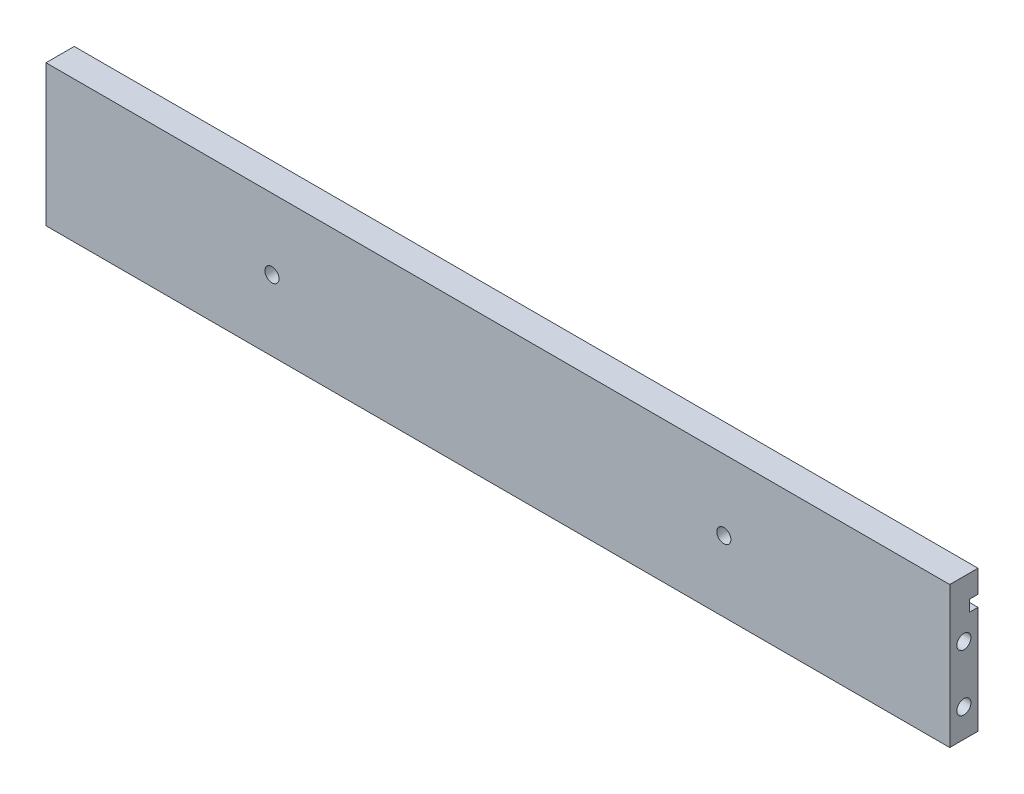
SolidWorks part; units mm, degrees
ref_plane "Ön Düzlem" through (0, 0, 0) normal (0, 0, 1) x (1, 0, 0)
ref_plane "Üst Düzlem" through (0, 0, 0) normal (0, 1, 0) x (1, 0, 0)
ref_plane "Sağ Düzlem" through (0, 0, 0) normal (1, 0, 0) x (0, 0, -1)
sketch "Sketch1" plane through (0, 0, 0) normal (0, 0, 1) x (1, 0, 0)
  line L1 (0, 0) -> (160, 0)
  line L2 (0, 0) -> (0, 25)
  line L3 (0, 25) -> (160, 25)
  line L4 (160, 0) -> (160, 25)
extrude "Boss-Extrude1" add sketch "Sketch1" along normal blind 5
sketch "Sketch2" plane through (0, 0, 0) normal (0, -1, 0) x (1, 0, 0)
  line L0 (0, 5) -> (0, 0) construction
  line L1 (160, 5) -> (160, 0) construction
  line L2 (0, 5) -> (160, 5) construction
  circle A0 centre (40, 2.5) radius 1.25
  circle A1 centre (120, 2.5) radius 1.24
  dimension "D1" = 40
  dimension "D2" = 40
  dimension "D3" = 2.5
  dimension "D4" = 2.5
extrude "Cut-Extrude1" cut sketch "Sketch2" against normal blind 10
cosmetic thread "Cosmetic Thread1" parameters "D2"=3
cosmetic thread "Cosmetic Thread2" parameters "D2"=3
sketch "Sketch5" plane through (0, 0, 0) normal (-1, 0, 0) x (0, 0, 1)
  line L0 (0, 25) -> (0, 0) construction
  line L1 (1.5, 21) -> (0, 21)
  line L2 (1.5, 21) -> (1.5, 19)
  line L3 (1.5, 19) -> (0, 19)
  line L4 (0, 21) -> (0, 19)
  line L5 (5, 25) -> (0, 25) construction
  dimension "D1" = 4
  dimension "D2" = 2
  dimension "D3" = 1.5
extrude "Cut-Extrude4" cut sketch "Sketch5" against normal through all
sketch "Sketch6" plane through (0, 0, 5) normal (0, 0, 1) x (1, 0, 0)
  line L0 (0, 25) -> (0, 0) construction
  line L1 (160, 25) -> (0, 25) construction
  line L2 (160, 0) -> (160, 25) construction
  circle A0 centre (40, 12.5) radius 1.25
  circle A1 centre (120, 12.5) radius 1.25
  dimension "D1" = 40
  dimension "D2" = 12.5
  dimension "D3" = 40
  dimension "D4" = 12.5
extrude "Cut-Extrude5" cut sketch "Sketch6" against normal blind 10
cosmetic thread "Cosmetic Thread3" parameters "D2"=3
cosmetic thread "Cosmetic Thread4" parameters "D2"=3
sketch "Sketch7" plane through (0, 0, 0) normal (-1, 0, 0) x (0, 0, 1)
  line L0 (5, 0) -> (0, 0) construction
  line L1 (5, 25) -> (5, 0) construction
  line L3 (0, 19) -> (0, 0) construction
  circle A0 centre (2.5, 5) radius 1.25
  circle A1 centre (2.5, 15) radius 1.25
  dimension "D1" = 5
  dimension "D2" = 2.5
  dimension "D3" = 2.5
  dimension "D4" = 10
extrude "Cut-Extrude6" cut sketch "Sketch7" against normal blind 10
cosmetic thread "Cosmetic Thread5" parameters "D2"=3
cosmetic thread "Cosmetic Thread6" parameters "D2"=3
sketch "Sketch8" plane through (160, 0, 0) normal (1, 0, 0) x (0, 0, -1)
  line L1 (-5, 0) -> (-5, 25) construction
  line L2 (0, 0) -> (0, 19) construction
  line L3 (-5, 0) -> (0, 0) construction
  circle A0 centre (-2.5, 5) radius 1.25
  circle A1 centre (-2.5, 15) radius 1.25
  dimension "D1" = 2.5
  dimension "D2" = 2.5
  dimension "D3" = 5
  dimension "D4" = 10
extrude "Cut-Extrude7" cut sketch "Sketch8" against normal blind 10
cosmetic thread "Cosmetic Thread7" parameters "D2"=3
cosmetic thread "Cosmetic Thread8" parameters "D2"=3
